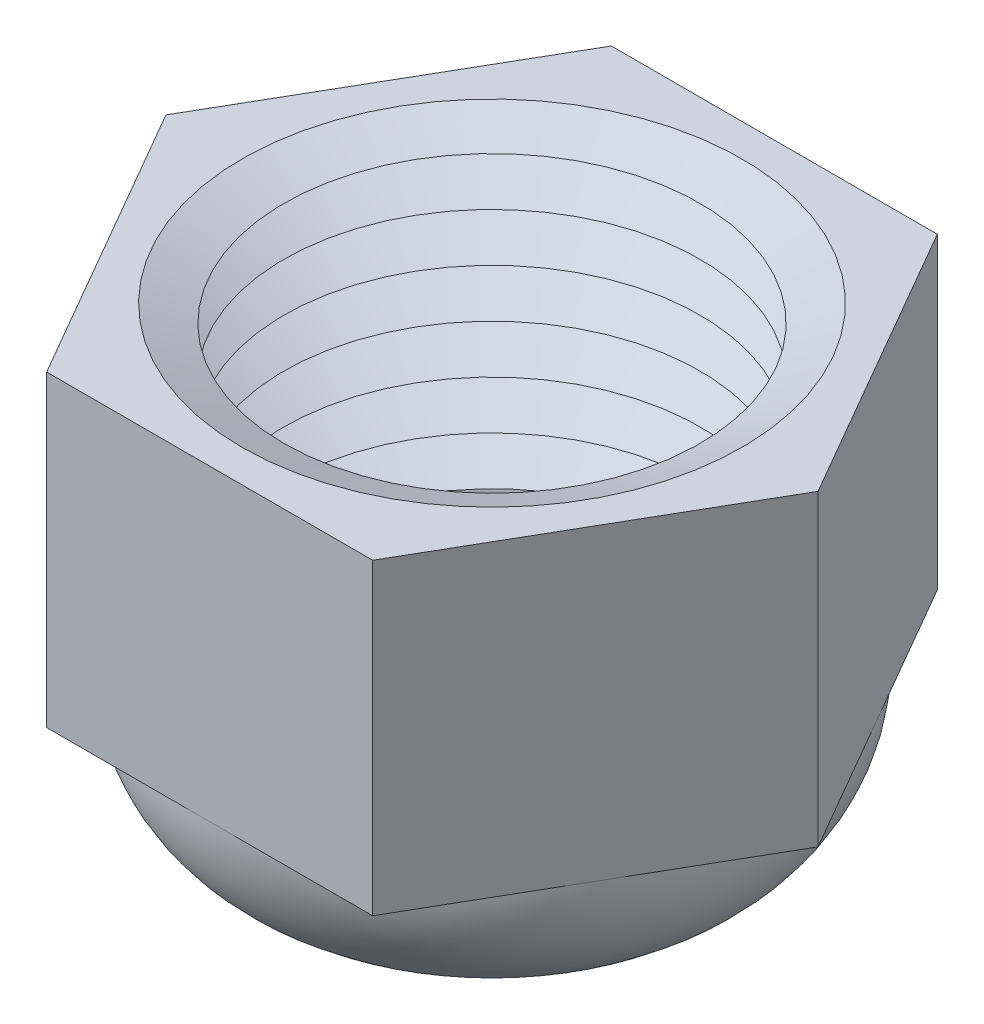
SolidWorks part; units mm, degrees
ref_plane "Front Plane" through (0, 0, 0) normal (0, 0, 1) x (1, 0, 0)
ref_plane "Top Plane" through (0, 0, 0) normal (0, 1, 0) x (1, 0, 0)
ref_plane "Right Plane" through (0, 0, 0) normal (1, 0, 0) x (0, 0, -1)
sketch "Sketch1" plane through (0, 0, 0) normal (0, 1, 0) x (1, 0, 0)
  line L1 (10.9697, 0) -> (5.4848, 9.5)
  line L2 (5.4848, 9.5) -> (-5.4848, 9.5)
  line L3 (-5.4848, 9.5) -> (-10.9697, 0)
  line L4 (-10.9697, 0) -> (-5.4848, -9.5)
  line L5 (-5.4848, -9.5) -> (5.4848, -9.5)
  line L6 (5.4848, -9.5) -> (10.9697, 0)
  circle A0 centre (0, 0) radius 9.5 construction
extrude "Boss-Extrude1" add sketch "Sketch1" along normal mid plane 10.36
sketch "Sketch2" plane through (0, 0, 0) normal (1, 0, 0) x (0, 0, -1)
  line L0 (-8.41, 5.18) -> (0, 5.18)
  line L1 (-9.5, -5.18) -> (0, -5.18) construction
  line L3 (0, 5.18) -> (0, -5.18)
  line L4 (-7, -5.18) -> (-8.41, -4.3659)
  line L5 (0, -5.18) -> (-7, -5.18)
  line L6 (-7, -3.5519) -> (-8.41, -4.3659)
  line L8 (-7, -3.5519) -> (-8.41, -2.7378)
  line L9 (-7, -1.9237) -> (-8.41, -2.7378)
  line L11 (-7, -1.9237) -> (-8.41, -1.1097)
  line L12 (-7, -0.2956) -> (-8.41, -1.1097)
  line L13 (-7, -0.2956) -> (-8.41, 0.5184)
  line L14 (-7, 1.3325) -> (-8.41, 0.5184)
  line L16 (-7, 1.3325) -> (-8.41, 2.1466)
  line L17 (-7, 2.9606) -> (-8.41, 2.1466)
  line L18 (-7, 2.9606) -> (-8.41, 3.7747)
  line L19 (-7, 4.5888) -> (-8.41, 3.7747)
  line L21 (-7, 4.5888) -> (-8.41, 5.18)
  line L22 (-9.5, 5.18) -> (0, 5.18) construction
ref_axis "Axis1" through (0, 5.698, 0) along (0, -1, 0)
revolve "Cut-Revolve1" cut sketch "Sketch2" angle 360 about L3
sketch "Sketch3" plane through (0, -5.18, 0) normal (0, -1, 0) x (1, 0, 0)
  circle A0 centre (0, 0) radius 9.5
extrude "Boss-Extrude2" add sketch "Sketch3" along normal blind 5
fillet "Fillet3" radius 5 1 edges at (0, -10.18, -9.5)
sketch "Sketch4" plane through (0, -10.18, 0) normal (0, -1, 0) x (1, 0, 0)
  circle A0 centre (0, 0) radius 6.9
  dimension "D1" = 13.8
extrude "Cut-Extrude1" cut sketch "Sketch4" against normal blind 5
fillet "Fillet4" radius 5 1 edges at (0, -5.18, -6.9)
